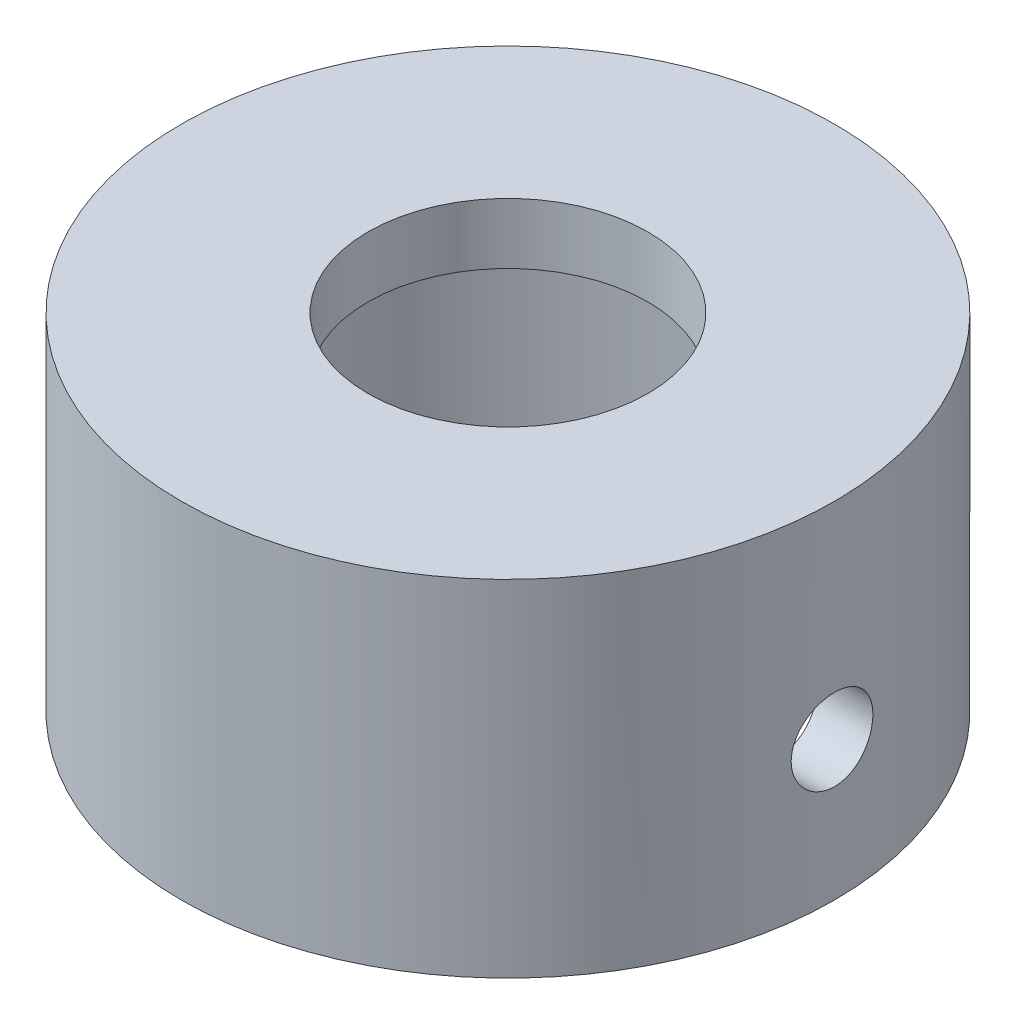
SolidWorks part; units mm, degrees
ref_plane "Front Plane" through (0, 0, 0) normal (0, 0, 1) x (1, 0, 0)
ref_plane "Top Plane" through (0, 0, 0) normal (0, 1, 0) x (1, 0, 0)
ref_plane "Right Plane" through (0, 0, 0) normal (1, 0, 0) x (0, 0, -1)
sketch "Sketch1" plane through (0, 0, 0) normal (0, 1, 0) x (1, 0, 0)
  circle A0 centre (0, 0) radius 22.225
  dimension "D2" = 44.45
extrude "Boss-Extrude1" add sketch "Sketch1" against normal blind 19.05
sketch "Sketch2" plane through (0, -19.05, 0) normal (0, -1, 0) x (1, 0, 0)
  circle A0 centre (0, 0) radius 18.542
  dimension "D1" = 37.084
extrude "Cut-Extrude1" cut sketch "Sketch2" against normal blind 13.3985
sketch "Sketch3" plane through (0, 0, 0) normal (0, 1, 0) x (1, 0, 0)
  circle A0 centre (0, 0) radius 9.525
  dimension "D1" = 19.05
extrude "Cut-Extrude2" cut sketch "Sketch3" against normal through all
sketch "Sketch4" plane through (0, -5.6515, 0) normal (0, -1, 0) x (1, 0, 0)
  circle A0 centre (0, 0) radius 15.875
  dimension "D1" = 31.75
extrude "Cut-Extrude3" cut sketch "Sketch4" against normal blind 1.524
sketch "Sketch5" plane through (0, 0, 0) normal (1, 0, 0) x (0, 0, -1)
  line L0 (-15.875, -4.1275) -> (15.875, -4.1275) construction
  circle A0 centre (0, -14.0335) radius 2.7781
  dimension "D1" = 5.5562
  dimension "D2" = 9.906
extrude "Cut-Extrude4" cut sketch "Sketch5" against normal through all and the other way through all
sketch "Sketch6" plane through (0, -19.05, 0) normal (0, -1, 0) x (1, 0, 0)
  circle A0 centre (0, 0) radius 22.225
extrude "Boss-Extrude2" add sketch "Sketch6" along normal blind 4.445
sketch "Sketch7" plane through (0, -23.495, 0) normal (0, -1, 0) x (1, 0, 0)
  circle A1 centre (0, 0) radius 18.542
  circle A2 centre (0, 0) radius 18.542 construction
  dimension "D1" = 0
extrude "Cut-Extrude5" cut sketch "Sketch7" against normal blind 6.35
